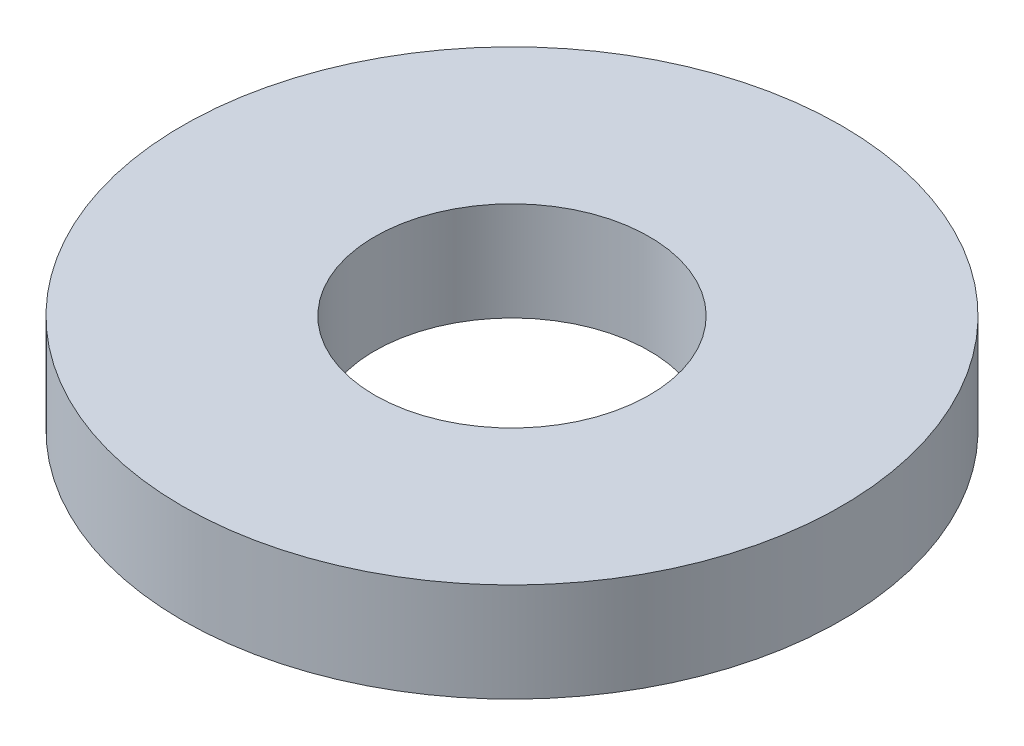
SolidWorks part; units mm, degrees
ref_plane "Front Plane" through (0, 0, 0) normal (0, 0, 1) x (1, 0, 0)
ref_plane "Top Plane" through (0, 0, 0) normal (0, 1, 0) x (1, 0, 0)
ref_plane "Right Plane" through (0, 0, 0) normal (1, 0, 0) x (0, 0, -1)
sketch "Sketch1" plane through (0, 0, 0) normal (0, 1, 0) x (1, 0, 0)
  circle A0 centre (0, 0) radius 60
  dimension "FLANGE_OD" = 120
extrude "Boss-Extrude1" add sketch "Sketch1" along normal blind 18
sketch "Sketch2" plane through (0, 0, 0) normal (0, 1, 0) x (1, 0, 0)
  circle A0 centre (0, 0) radius 25
  dimension "BORE_D" = 50
extrude "Cut-Extrude1" cut sketch "Sketch2" along normal through all
sketch "Sketch3" plane through (0, 18, 0) normal (0, 1, 0) x (1, 0, 0)
  circle A0 centre (0, 0) radius 15.2575 construction
  circle A1 centre (-15.2575, 0) radius 2.5134
  dimension "BOLT_D" = 5.0268
  dimension "BOLT_PCD" = 30.515
extrude "Cut-Extrude2" cut sketch "Sketch3" against normal blind 14.0621 rebuild error yes
pattern_circular "CirPattern1" count 8 over 360 rebuild error yes
